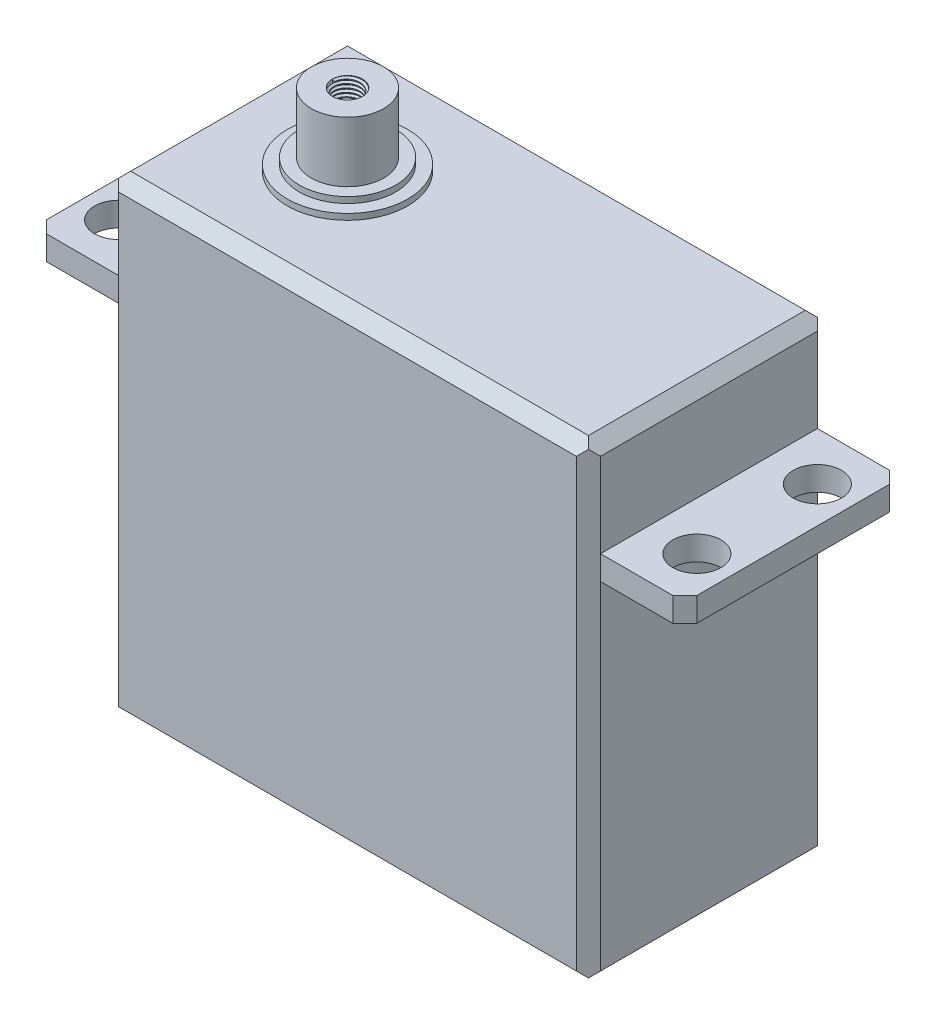
SolidWorks part; units mm, degrees
ref_plane "前视基准面" through (0, 0, 0) normal (0, 0, 1) x (1, 0, 0)
ref_plane "上视基准面" through (0, 0, 0) normal (0, 1, 0) x (1, 0, 0)
ref_plane "右视基准面" through (0, 0, 0) normal (1, 0, 0) x (0, 0, -1)
other "Configuration Table"
sketch "草图1" plane through (0, 0, 0) normal (0, 0, 1) x (1, 0, 0)
  line L0 (20, -18.5) -> (19, -19.5)
  line L1 (-19, 19.5) -> (19, 19.5)
  line L2 (-20, 18.5) -> (-20, -18.5)
  line L3 (-19, -19.5) -> (19, -19.5)
  line L4 (20, 18.5) -> (20, -18.5)
  line L5 (-20, 19.5) -> (20, -19.5) construction
  line L6 (-20, -19.5) -> (20, 19.5) construction
  line L7 (-20, -18.5) -> (-19, -19.5)
  line L8 (-19, 19.5) -> (-20, 18.5)
  line L9 (19, 19.5) -> (20, 18.5)
  point P0 (0, 0)
  dimension "D1" = 40
  dimension "D2" = 39
extrude "凸台-拉伸1" add sketch "草图1" along normal blind 20
sketch "草图2" plane through (0, 19.5, 0) normal (0, 1, 0) x (1, 0, 0)
  line L0 (19, 0) -> (-19, 0) construction
  line L1 (-19, -20) -> (-19, 0) construction
  circle A0 centre (-10, -10) radius 4
  dimension "D1" = 8
  dimension "D2" = 10
  dimension "D3" = 9
extrude "凸台-拉伸2" add sketch "草图2" along normal blind 1
sketch "草图3" plane through (0, 20.5, 0) normal (0, 1, 0) x (1, 0, 0)
  line L0 (19, 0) -> (-19, 0) construction
  line L1 (-19, -20) -> (-19, 0) construction
  circle A0 centre (-10, -10) radius 3
  point P6 (-18.1312, -9.9579)
  dimension "D1" = 6
  dimension "D2" = 10
  dimension "D3" = 9
extrude "凸台-拉伸3" add sketch "草图3" along normal blind 5
chamfer "倒角1" distance 1 angle 45 6 edges at (0, 19.5, 0) (0, 19.5, 20) (20, 0, 0) (20, 0, 20) (-20, 0, 20) (-20, 0, 0)
sketch "草图5" plane through (-20, 0, 0) normal (-1, 0, 0) x (0, 0, 1)
  line L0 (1, 11.5) -> (19, 11.5)
  line L1 (1, 18.5) -> (1, -18.5) construction
  line L2 (19, -18.5) -> (19, 18.5) construction
  line L3 (20, -19.5) -> (0, -19.5) construction
  line L4 (1, 11.5) -> (1, 9.5)
  line L5 (1, 9.5) -> (19, 9.5)
  line L6 (19, 9.5) -> (19, 11.5)
  dimension "D1" = 31
  dimension "D2" = 2
extrude "凸台-拉伸4" add sketch "草图5" along normal blind 7
sketch "草图6" plane through (20, 0, 0) normal (1, 0, 0) x (0, 0, -1)
  line L0 (-19, 11.5) -> (-1, 11.5)
  line L1 (-19, 18.5) -> (-19, -18.5) construction
  line L2 (-1, -18.5) -> (-1, 18.5) construction
  line L3 (-20, -19.5) -> (0, -19.5) construction
  line L4 (-19, 11.5) -> (-19, 9.5)
  line L5 (-19, 9.5) -> (-1, 9.5)
  line L6 (-1, 9.5) -> (-1, 11.5)
  dimension "D1" = 31
  dimension "D2" = 2
extrude "凸台-拉伸5" add sketch "草图6" along normal blind 7
sketch "草图7" plane through (0, 11.5, 0) normal (0, 1, 0) x (1, 0, 0)
  line L0 (-27, -1) -> (-20, -1) construction
  line L2 (-20, -19) -> (-20, -1) construction
  line L3 (-34.5279, -10) -> (-5.3298, -10) construction
  line L4 (0, -10) -> (0, 9.9499) construction
  circle A0 centre (-24, -5) radius 2
  circle A3 centre (-24, -15) radius 2
  circle A4 centre (24, -15) radius 2
  circle A5 centre (24, -5) radius 2
  dimension "D1" = 4
  dimension "D2" = 4
  dimension "D3" = 4
  dimension "D4" = 10
extrude "切除-拉伸1" cut sketch "草图7" against normal through all
chamfer "倒角2" distance 1 angle 45 4 edges at (27, 10.5, 1) (27, 10.5, 19) (-27, 10.5, 19) (-27, 10.5, 1)
sketch "草图8" plane through (0, 25.5, 0) normal (0, 1, 0) x (1, 0, 0)
  circle A0 centre (-10, -10) radius 1.25
  dimension "D1" = 2.5
extrude "切除-拉伸2" cut sketch "草图8" against normal blind 5
sketch "草图9" plane through (0, 19.5, 0) normal (0, 1, 0) x (1, 0, 0)
  circle A0 centre (-10, -10) radius 5
extrude "凸台-拉伸6" add sketch "草图9" along normal blind 0.5
thread "螺纹线2" pitch 0.3175 method extrude profile "螺纹线轮廓3" start angle 0, offset 0, length 5, pitch 0.3175, diameter 2.5
ref_plane "基准面3" through (-11.25, 25.5, 10) normal (0, 0, 1) x (-1, 0, 0)
sketch "螺纹线轮廓3" plane through (-11.25, 25.5, 10) normal (0, 0, 1) x (-1, 0, 0)
  line L0 (0, 0) -> (0, 0.3175) construction
  line L11 (0, 0) -> (0, 0.2778)
  line L12 (0, 0.2778) -> (-0.1719, 0.1786)
  line L13 (-0.1719, 0.1786) -> (-0.1719, 0.0992)
  line L15 (-0.1719, 0.0992) -> (0, 0)
  line L17 (-0.1719, 0.1389) -> (0, 0.1389) construction
  point P2 (0, 0)
  dimension "Pitch" = 0.3175
  dimension "Profile_Angle" = 60
  dimension "Profile_Land" = 0.0794
  dimension "Profile_Height" = 0.1719
chamfer "倒角3" distance 1 angle 45 2 edges at (0, -19.5, 20) (0, -19.5, 0)
